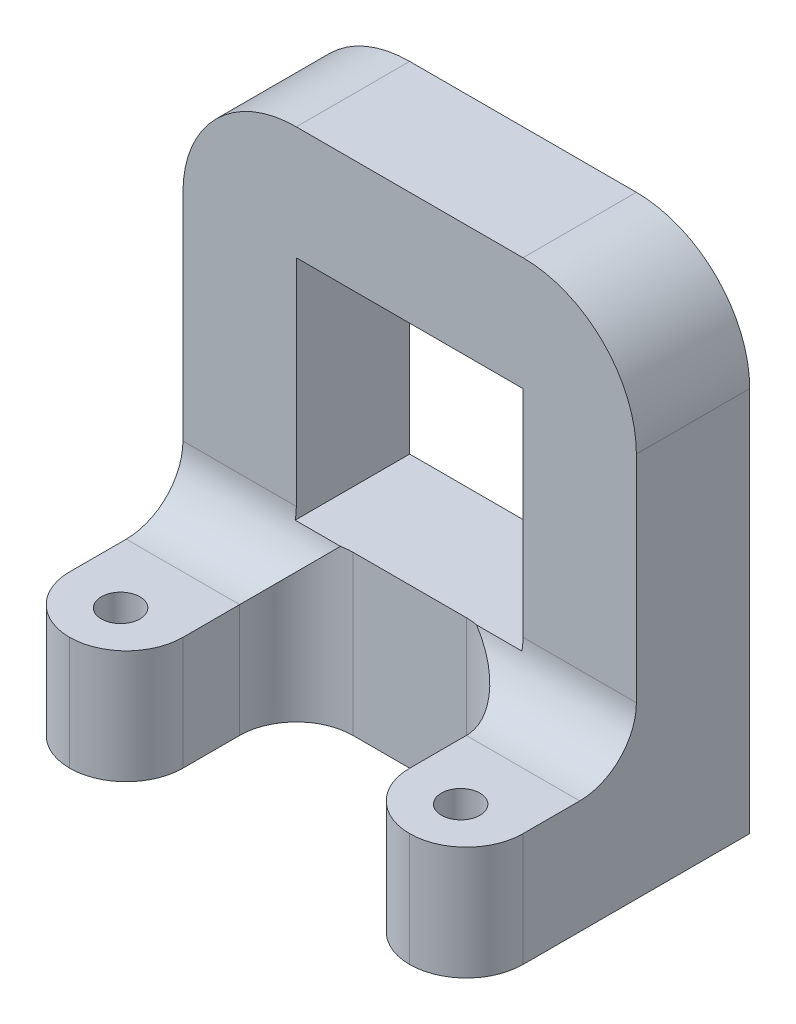
SolidWorks part; units mm, degrees
ref_plane "Plan de face" through (0, 0, 0) normal (0, 0, 1) x (1, 0, 0)
ref_plane "Plan de dessus" through (0, 0, 0) normal (0, 1, 0) x (1, 0, 0)
ref_plane "Plan de droite" through (0, 0, 0) normal (1, 0, 0) x (0, 0, -1)
sketch "Esquisse1" plane through (0, 0, 0) normal (0, 0, 1) x (1, 0, 0)
  line L0 (0, 0) -> (40, 0)
  line L1 (0, 0) -> (40, 0) construction
  line L2 (0, 0) -> (0, 44) construction
  line L3 (0, 44) -> (40, 44) construction
  line L4 (40, 0) -> (40, 44) construction
  line L5 (40, 0) -> (40, 44)
  line L6 (40, 44) -> (0, 44)
  line L7 (0, 44) -> (0, 0)
  line L9 (10, 34) -> (30, 34)
  line L10 (10, 34) -> (10, 14)
  line L11 (10, 14) -> (30, 14)
  line L12 (30, 34) -> (30, 14)
  dimension "D1" = 40
  dimension "D2" = 44
  dimension "D3" = 10
  dimension "D4" = 10
  dimension "D5" = 10
  dimension "D6" = 14
extrude "Boss.-Extru.1" add sketch "Esquisse1" along normal blind 10
sketch "Esquisse3" plane through (0, 0, 10) normal (0, 0, 1) x (1, 0, 0)
  line L0 (30, 0) -> (40, 0)
  line L3 (0, 10) -> (10, 10)
  line L4 (0, 44) -> (0, 0)
  line L5 (0, 0) -> (40, 0)
  line L6 (40, 0) -> (40, 44)
  line L7 (40, 44) -> (0, 44)
  line L8 (0, 10) -> (0, 0)
  line L9 (0, 0) -> (10, 0)
  line L12 (10, 0) -> (10, 10)
  line L14 (40, 0) -> (40, 10)
  line L15 (40, 10) -> (30, 10)
  line L16 (30, 0) -> (30, 10)
  line L17 (0, 0) -> (40, 0) construction
  dimension "D3" = 10
  dimension "D4" = 10
  dimension "D5" = 10
  dimension "D2" = 10
extrude "Boss.-Extru.2" add sketch "Esquisse3" along normal blind 15
sketch "Esquisse4" plane through (0, 10, 0) normal (0, 1, 0) x (1, 0, 0)
  line L0 (0, -25) -> (0, -10) construction
  line L2 (40, -25) -> (40, -10) construction
  line L4 (40, -25) -> (30, -25) construction
  line L5 (10, -25) -> (0, -25) construction
  circle A0 centre (5, -20.5) radius 1.5
  circle A1 centre (35, -20.5) radius 1.5
  dimension "D3" = 3
  dimension "D4" = 3
  dimension "D1" = 5
  dimension "D5" = 5
  dimension "D2" = 4.5
  dimension "D6" = 4.5
hole_wizard "Dégagement M31" positions "Esquisse5" profile "Esquisse6" hole size "M3" standard "ISO" end condition through all
sketch "Esquisse5" plane through (0, 10, 0) normal (0, 1, 0) x (1, 0, 0)
  point P0 (5, -20.5)
  point P3 (35, -20.5)
sketch "Esquisse6" plane through (5, 10, 20.5) normal (1, 0, 0) x (0, 0, 1)
  line L0 (0, 0) -> (0, 10)
  line L1 (0, 10) -> (1.7, 10)
  line L2 (1.7, 10) -> (1.7, 0)
  line L5 (1.7, 0) -> (0, 0)
  line L11 (0, -6.35) -> (0, 107.95) construction
  dimension "Diamètre du perçage jusqu'au prochain" = 3.4
  dimension "Profondeur du perçage jusqu'au prochain" = 10
ref_plane "Plan1" through (0, 0, 5) normal (0, 0, 1) x (1, 0, 0)
fillet "Congé2" radius 10 2 edges at (0, 44, 5) (40, 44, 5)
fillet "Congé3" radius 5 8 edges at (35, 10, 10) (5, 10, 10) (30, 5, 10) (10, 5, 10) (40, 5, 25) (30, 5, 25) (10, 5, 25) (0, 5, 25)
equation "\"largeur_cremail\"= 20"
equation "\"hauteur_cremail\"= 20"
equation "\"epaiss_cadre\"= 10"
equation "\"hauteur_basecremail_sol\"= 4"
equation "\"D1@Esquisse1\"=\"largeur_cremail\"+\"epaiss_cadre\"*2"
equation "\"D2@Esquisse1\"=\"hauteur_basecremail_sol\"+\"hauteur_cremail\"+\"epaiss_cadre\"*2"
equation "\"D3@Esquisse1\"=\"epaiss_cadre\""
equation "\"D4@Esquisse1\"=\"epaiss_cadre\""
equation "\"D5@Esquisse1\"=\"epaiss_cadre\""
equation "\"D6@Esquisse1\"=\"hauteur_basecremail_sol\"+\"epaiss_cadre\""
equation "\"D1@Boss.-Extru.1\"=\"epaiss_cadre\""
equation "\"D2@Esquisse3\"=\"epaiss_cadre\""
equation "\"D4@Esquisse3\"=\"epaiss_cadre\""
equation "\"D5@Esquisse3\"=\"D3@Esquisse3\""
equation "\"D1@Esquisse4\"=\"epaiss_cadre\"/2"
equation "\"D5@Esquisse4\"=\"epaiss_cadre\"/2"
